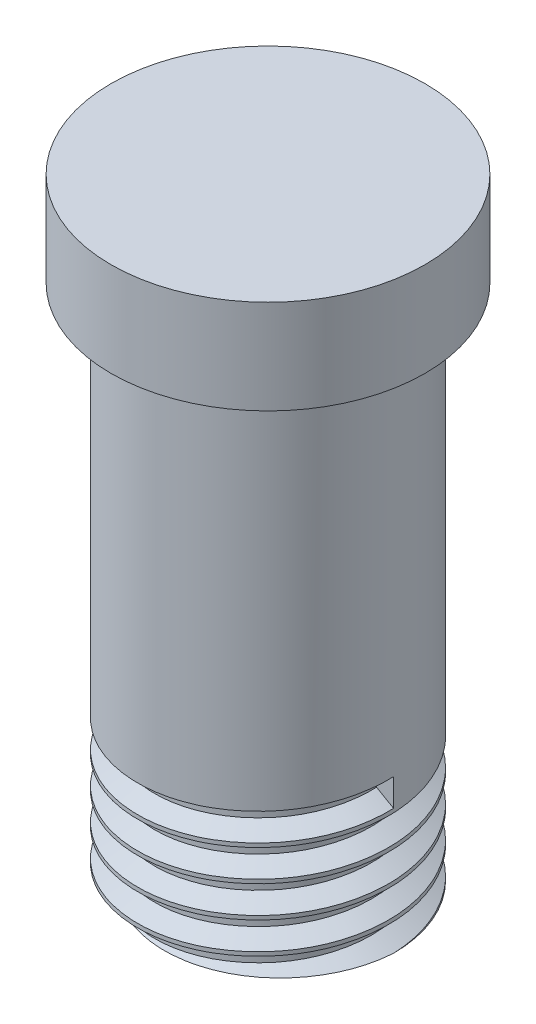
SolidWorks part; units mm, degrees
ref_plane "Front Plane" through (0, 0, 0) normal (0, 0, 1) x (1, 0, 0)
ref_plane "Top Plane" through (0, 0, 0) normal (0, 1, 0) x (1, 0, 0)
ref_plane "Right Plane" through (0, 0, 0) normal (1, 0, 0) x (0, 0, -1)
sketch "Sketch2" plane through (0, 0, 0) normal (0, 1, 0) x (1, 0, 0)
  circle A0 centre (0, 0) radius 4
  dimension "D1" = 8
extrude "Boss-Extrude1" add sketch "Sketch2" along normal blind 12.5
sketch "Sketch3" plane through (0, 12.5, 0) normal (0, 1, 0) x (1, 0, 0)
  circle A0 centre (0, 0) radius 5
  dimension "D1" = 10
extrude "Boss-Extrude2" add sketch "Sketch3" along normal blind 3
sketch "Sketch5" plane through (0, 0, 0) normal (0, -1, 0) x (1, 0, 0)
  circle A0 centre (0, 0) radius 4
extrude "Boss-Extrude3" add sketch "Sketch5" along normal blind 4
thread "Thread1" pitch 1 method cut profile "Thread Profile1" start angle 0, offset 1, length 5, pitch 1, diameter 8
ref_plane "Plane1" through (4, -5, 0) normal (0, 0, 1) x (1, 0, 0)
sketch "Thread Profile1" plane through (4, -5, 0) normal (0, 0, 1) x (1, 0, 0)
  line L0 (0, 0) -> (0, 1) construction
  line L11 (0, 0) -> (0, 0.875)
  line L12 (0, 0.875) -> (-0.5413, 0.5625)
  line L13 (-0.5413, 0.5625) -> (-0.5413, 0.3125)
  line L15 (-0.5413, 0.3125) -> (0, 0)
  line L17 (-0.5413, 0.4375) -> (0, 0.4375) construction
  point P2 (0, 0)
  dimension "Pitch" = 1
  dimension "Profile_Angle" = 60
  dimension "Profile_Land" = 0.25
  dimension "Profile_Height" = 0.5413
